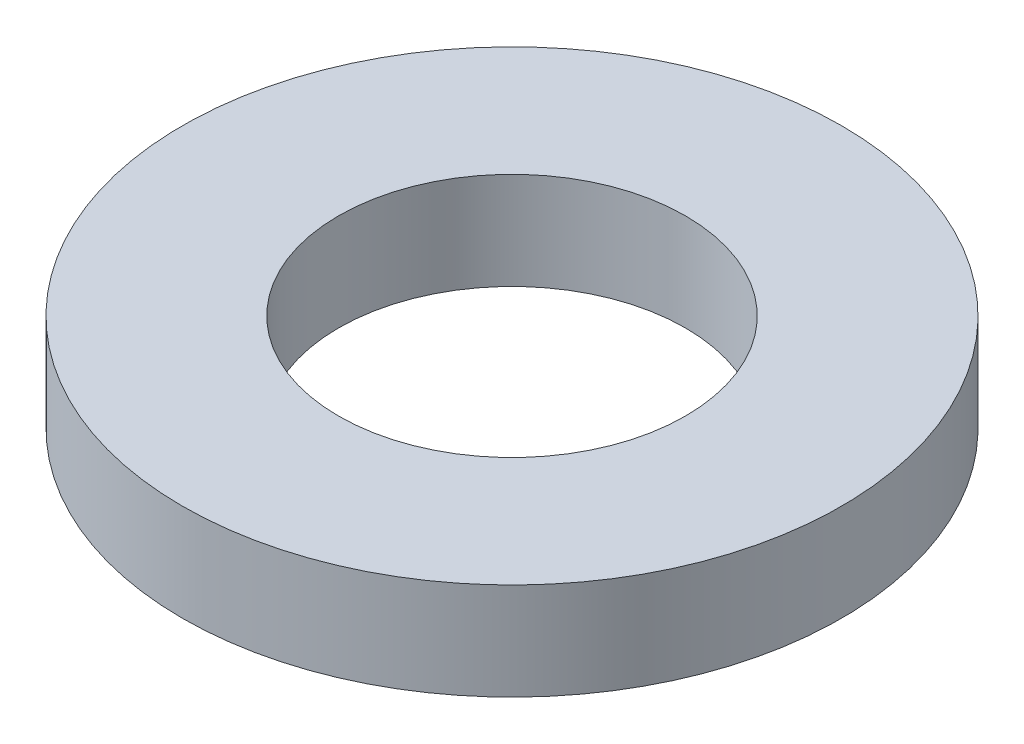
SolidWorks part; units mm, degrees
ref_plane "Front Plane" through (0, 0, 0) normal (0, 0, 1) x (1, 0, 0)
ref_plane "Top Plane" through (0, 0, 0) normal (0, 1, 0) x (1, 0, 0)
ref_plane "Right Plane" through (0, 0, 0) normal (1, 0, 0) x (0, 0, -1)
sketch "Sketch1" plane through (0, 0, 0) normal (0, 1, 0) x (1, 0, 0)
  circle A0 centre (0, 0) radius 47.5
  dimension "FLANGE_OD" = 95
extrude "Boss-Extrude1" add sketch "Sketch1" along normal blind 14
sketch "Sketch2" plane through (0, 0, 0) normal (0, 1, 0) x (1, 0, 0)
  circle A0 centre (0, 0) radius 25
  dimension "BORE_D" = 50
extrude "Cut-Extrude1" cut sketch "Sketch2" along normal through all
sketch "Sketch3" plane through (0, 14, 0) normal (0, 1, 0) x (1, 0, 0)
  circle A0 centre (0, 0) radius 16.5666 construction
  circle A1 centre (-16.5666, 0) radius 3.569
  dimension "BOLT_D" = 7.138
  dimension "BOLT_PCD" = 33.1333
extrude "Cut-Extrude2" cut sketch "Sketch3" against normal blind 13.3184 rebuild error yes
pattern_circular "CirPattern1" count 8 over 360 rebuild error yes
